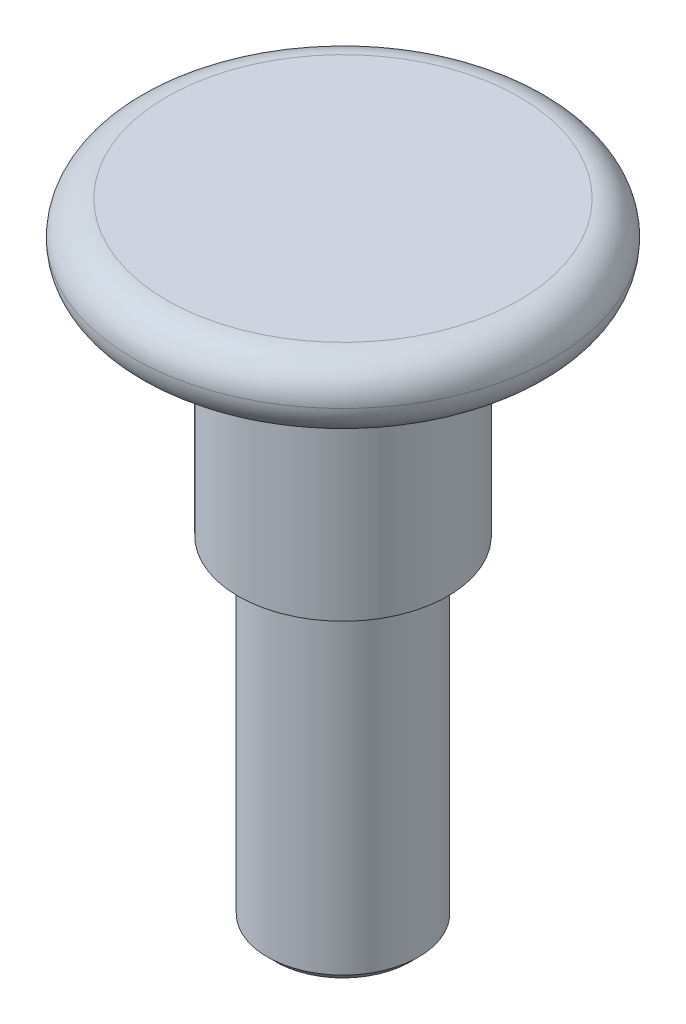
SolidWorks part; units mm, degrees
ref_plane "Plano frontal" through (0, 0, 0) normal (0, 0, 1) x (1, 0, 0)
ref_plane "Plano superior" through (0, 0, 0) normal (0, 1, 0) x (1, 0, 0)
ref_plane "Plano direito" through (0, 0, 0) normal (1, 0, 0) x (0, 0, -1)
sketch "Esboço1" plane through (0, 0, 0) normal (0, 0, 1) x (1, 0, 0)
  line L0 (0, -62.7616) -> (0, 56.5452) construction
  line L1 (0, 56.5452) -> (12.5, 56.5452)
  line L2 (12.5, 56.5452) -> (12.5, 52.5452)
  line L3 (12.5, 52.5452) -> (6.25, 52.5452)
  line L4 (6.25, 52.5452) -> (6.25, 39.1452)
  line L5 (6.25, 39.1452) -> (4.5, 39.1452)
  line L6 (4.5, 39.1452) -> (4.5, 19.1452)
  line L7 (4.5, 19.1452) -> (0, 19.1452)
  line L8 (0, 56.5452) -> (0, 19.1452)
  dimension "D1" = 12.5
  dimension "D2" = 6.25
  dimension "D3" = 4.5
  dimension "D4" = 4
  dimension "D5" = 13.4
  dimension "D6" = 20
revolve "Revolução1" add sketch "Esboço1" angle 360 about L0
fillet "Filete2" radius 2 2 edges at (0, 52.5452, -12.5) (0, 56.5452, -12.5)
chamfer "Chanfro1" distance 0.5 angle 45 1 edges at (0, 19.1452, -4.5)
